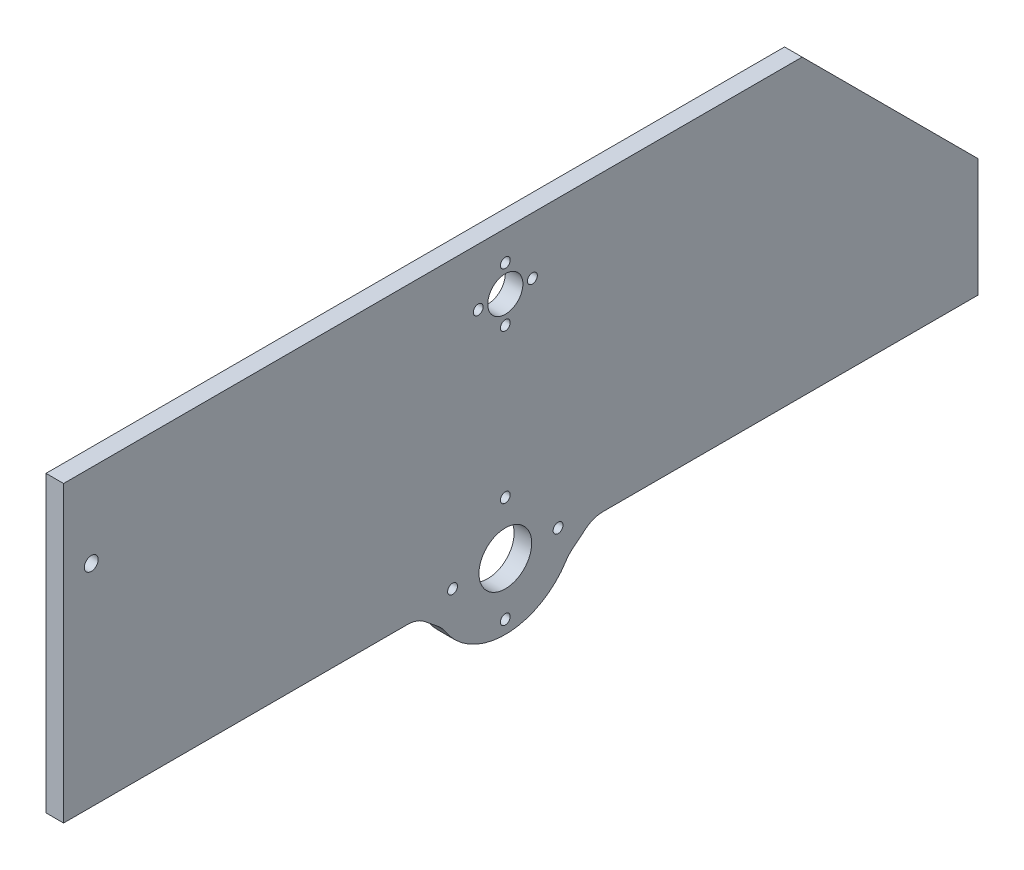
SolidWorks part; units mm, degrees
ref_plane "Front Plane" through (0, 0, 0) normal (0, 0, 1) x (1, 0, 0)
ref_plane "Top Plane" through (0, 0, 0) normal (0, 1, 0) x (1, 0, 0)
ref_plane "Right Plane" through (0, 0, 0) normal (1, 0, 0) x (0, 0, -1)
sketch "Sketch1" plane through (0, 0, 0) normal (1, 0, 0) x (0, 0, -1)
  line L0 (330.2, 63.5) -> (266.7, 127)
  line L1 (0, 0) -> (330.2, 0)
  line L2 (0, 0) -> (0, 127)
  line L3 (0, 127) -> (266.7, 127)
  line L4 (330.2, 0) -> (330.2, 63.5)
  point P7 (0, 0)
  dimension "D1" = 330.2
  dimension "D2" = 127
extrude "Main Plate Size" add sketch "Sketch1" along normal blind 6.35
sketch "Sketch2" plane through (6.35, 0, 0) normal (1, 0, 0) x (0, 0, -1)
  line L0 (178.562, 23.8252) -> (159.512, 42.8752) construction
  line L1 (0, 0) -> (330.2, 0) construction
  line L2 (178.562, 23.8252) -> (159.512, 4.7752) construction
  line L3 (159.512, 42.8752) -> (140.462, 23.8252) construction
  line L4 (159.512, 4.7752) -> (140.462, 23.8252) construction
  line L5 (178.562, 23.8252) -> (140.462, 23.8252) construction
  line L6 (159.512, 42.8752) -> (159.512, 4.7752) construction
  line L7 (0, 127) -> (0, 0) construction
  line L9 (0, 20.8026) -> (134.112, 20.8026)
  line L10 (184.912, 20.8026) -> (330.2, 20.8026)
  line L11 (330.2, 0) -> (330.2, 63.5) construction
  line L12 (0, 20.8026) -> (0, 0)
  line L13 (330.2, 0) -> (330.2, 20.8026)
  line L15 (0, 0) -> (177.8, 0)
  line L16 (177.8, 0) -> (330.2, 0)
  circle A0 centre (159.512, 23.8252) radius 9.525
  circle A1 centre (159.512, 42.8752) radius 1.778
  circle A2 centre (178.562, 23.8252) radius 1.778
  circle A3 centre (159.512, 4.7752) radius 1.778
  circle A4 centre (140.462, 23.8252) radius 1.778
  arc A5 (134.112, 20.8026) -> (184.912, 20.8026) centre (159.512, 25.908) ccw
  point P24 (134.112, 20.8026)
  line M11 (0, 127) -> (0, 0)
  line M12 (0, 0) -> (330.2, 0)
  line M13 (330.2, 0) -> (330.2, 63.5)
  dimension "D1" = 19.05
  dimension "D2" = 3.556
  dimension "D6" = 25.908
  dimension "D3" = 38.1
  dimension "D4" = 159.512
  dimension "D5" = 5.1054
  dimension "D7" = 2.0828
extrude "Bottom Shaft Mounting Holes" cut sketch "Sketch2" against normal through all contours A5 L9 M11 M12 | A5 L10 M12 M13 | A0 | A3 | A2 | A1 | A4 region at (6.35, 10.1874, -254.2605) region at (6.35, 10.1704, -70.3601) region at (6.35, 23.8252, -159.512) region at (6.35, 42.8752, -159.512) region at (6.35, 23.8252, -178.562) region at (6.35, 4.7752, -159.512) region at (6.35, 23.8252, -140.462)
sketch "Sketch3" plane through (6.35, 0, 0) normal (1, 0, 0) x (0, 0, -1)
  line L0 (159.512, 23.8252) -> (159.512, 106.5022) construction
  line L2 (159.512, 116.2812) -> (149.733, 106.5022) construction
  line L3 (149.733, 106.5022) -> (159.512, 96.7232) construction
  line L4 (159.512, 96.7232) -> (169.291, 106.5022) construction
  line L5 (169.291, 106.5022) -> (159.512, 116.2812) construction
  circle A0 centre (159.512, 106.5022) radius 6.35
  circle A1 centre (159.512, 106.5022) radius 9.779 construction
  circle A2 centre (149.733, 106.5022) radius 1.778
  circle A3 centre (159.512, 116.2812) radius 1.778
  circle A4 centre (169.291, 106.5022) radius 1.778
  circle A5 centre (159.512, 96.7232) radius 1.778
  dimension "D2" = 12.7
  dimension "D3" = 19.558
  dimension "D4" = 3.556
  dimension "D1" = 82.677
extrude "Top Battery Box Mounting Holes" cut sketch "Sketch3" against normal through all
chamfer "This is to match the idiotic Design of B Box" distance 6.35 distance2 6.35 2 edges at (3.175, 20.8026, -184.912) (3.175, 20.8026, -134.112)
fillet "This is to match the idiotic Design of B Box2" radius 10 4 edges at (3.175, 20.8026, -191.262) (3.175, 13.366, -182.1818) (3.175, 13.366, -136.8422) (3.175, 20.8026, -127.762)
sketch "Sketch4" plane through (6.35, 0, 0) normal (1, 0, 0) x (0, 0, -1)
  line L0 (0, 127) -> (0, 20.8026) construction
  line L1 (20, 87.0026) -> (0, 87.0026) construction
  line L2 (20, 87.0026) -> (20, 107.0026) construction
  line L3 (20, 107.0026) -> (0, 107.0026) construction
  line L4 (0, 87.0026) -> (0, 107.0026) construction
  line L5 (20, 87.0026) -> (0, 107.0026) construction
  line L6 (20, 107.0026) -> (0, 87.0026) construction
  line L7 (0, 20.8026) -> (124.1896, 20.8026) construction
  circle A0 centre (10, 97.0026) radius 2.5
  point P0 (10, 97.0026)
  dimension "D2" = 5
  dimension "D1" = 20
  dimension "D3" = 76.2
extrude "20mm Extrusion Mount" cut sketch "Sketch4" against normal through all
sketch "Sketch5" plane through (6.35, 0, 0) normal (1, 0, 0) x (0, 0, -1)
  line L0 (20, 87.0026) -> (0, 87.0026) construction
  line L1 (20, 87.0026) -> (0, 87.0026)
  line L2 (20, 87.0026) -> (20, 20.8026)
  line L3 (0, 20.8026) -> (124.1896, 20.8026) construction
  line L4 (0, 87.0026) -> (0, 20.8026)
  line L5 (0, 20.8026) -> (20, 20.8026)
